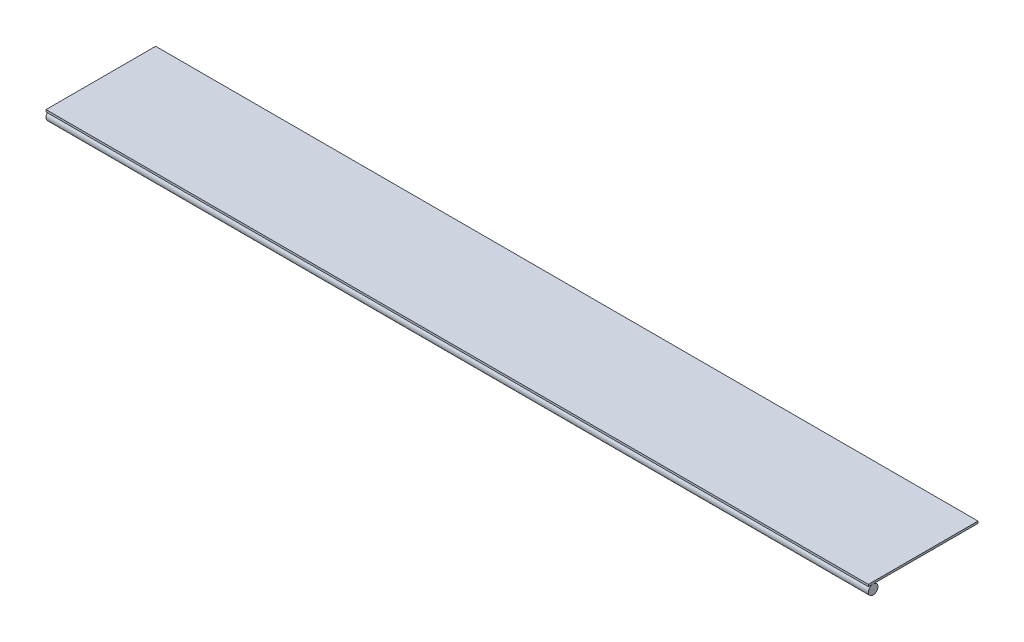
SolidWorks part; units mm, degrees
ref_plane "Front Plane" through (0, 0, 0) normal (0, 0, 1) x (1, 0, 0)
ref_plane "Top Plane" through (0, 0, 0) normal (0, 1, 0) x (1, 0, 0)
ref_plane "Right Plane" through (0, 0, 0) normal (1, 0, 0) x (0, 0, -1)
sketch "Sketch1" plane through (0, 0, 0) normal (0, 1, 0) x (1, 0, 0)
  line L1 (150, -20) -> (-150, -20)
  line L2 (150, -20) -> (150, 20)
  line L3 (150, 20) -> (-150, 20)
  line L4 (-150, -20) -> (-150, 20)
  line L5 (150, -20) -> (-150, 20) construction
  line L6 (150, 20) -> (-150, -20) construction
  point P0 (0, 0)
  dimension "D1" = 40
  dimension "D2" = 300
base flange "Base-Flange1" sketch "Sketch1" thickness 0.75 reverse thickness direction yes parameters "D1"=0.7366
sketch "Sketch6" plane through (150, 0, 0) normal (1, 0, 0) x (0, 0, -1)
  line L0 (-20, 0) -> (20, 0) construction
  line L1 (-20, 0.75) -> (-20, 0) construction
  circle A0 centre (-18.24, -1.76) radius 1.76
  dimension "D1" = 1.76
  dimension "D2" = 1.76
extrude "Boss-Extrude1" add sketch "Sketch6" against normal blind 300 separate body
sketch "Bend-Lines1" [suppressed] plane through (0, 0, 0) normal (0, 1, 0) x (1, 0, 0)
sketch "Bounding-Box1" [suppressed] plane through (0, 0, 0) normal (0, 1, 0) x (1, 0, 0)
sheet metal parameters "Sheet-Metal1" thickness 0.75 parameters "D1"=0.7366
flat pattern "Flat-Pattern1" [suppressed]
sketch "Bend-Lines2" plane through (0, 0, 0) normal (0, 1, 0) x (1, 0, 0)
sketch3d "Bounding-Box2" [suppressed]
  line L0 (150, -20, 0) -> (-150, -20, 0) construction
  line L1 (150, 20, 0) -> (-150, 20, 0) construction
  line L2 (150, -20, 0) -> (150, 20, 0) construction
  line L3 (-150, -20, 0) -> (-150, 20, 0) construction
